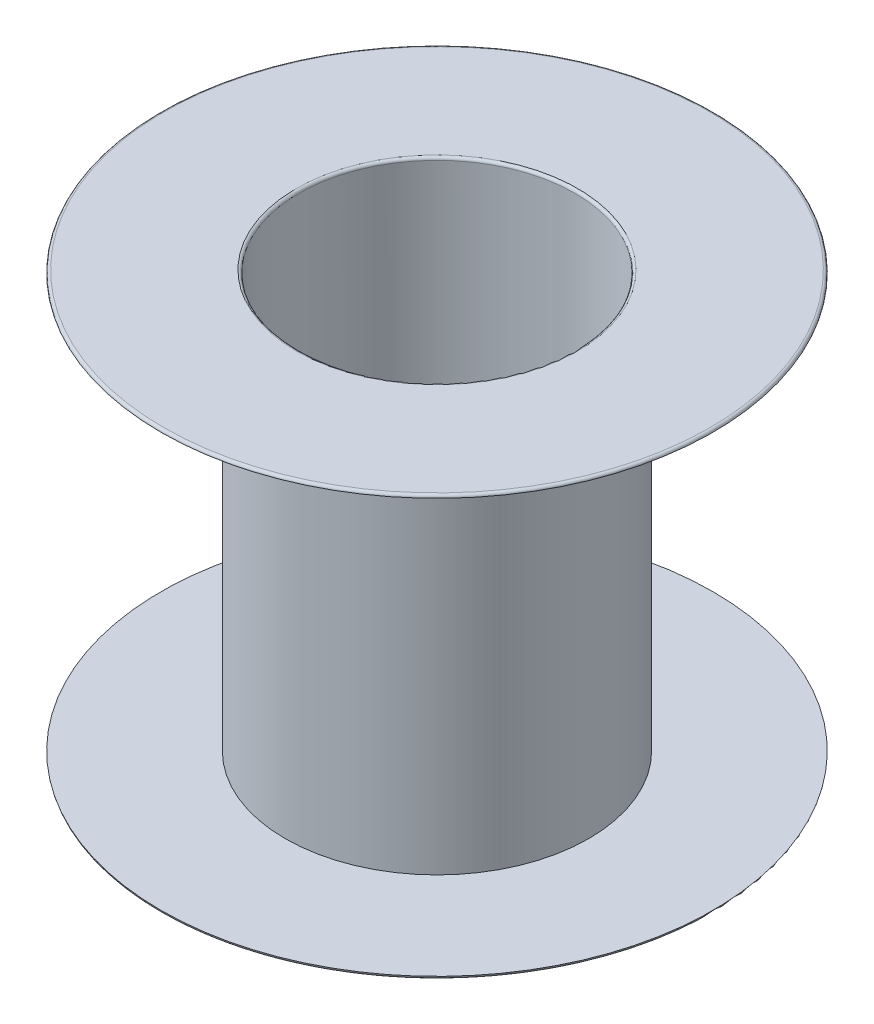
SolidWorks part; units mm, degrees
material "Copper"
ref_plane "Front" through (0, 0, 0) normal (0, 0, 1) x (1, 0, 0)
ref_plane "Top" through (0, 0, 0) normal (0, 1, 0) x (1, 0, 0)
ref_plane "Right" through (0, 0, 0) normal (1, 0, 0) x (0, 0, -1)
sketch "Sketch1" plane through (0, 0, 0) normal (0, 1, 0) x (1, 0, 0)
  circle A0 centre (0, 0) radius 0.5
  circle A1 centre (0, 0) radius 0.55
extrude "Boss-Extrude1" add sketch "Sketch1" along normal blind 1.5
ref_plane "Plane1" through (0, 0.75, 0) normal (0, 1, 0) x (1, 0, 0)
sketch "Sketch2" plane through (0, 1.5, 0) normal (0, 1, 0) x (1, 0, 0)
  circle A0 centre (0, 0) radius 0.5
  circle A1 centre (0, 0) radius 1
extrude "Boss-Extrude2" add sketch "Sketch2" along normal blind 0.01
fillet "Fillet1" radius 0.01 2 edges at (0, 1.51, 0.5) (0, 1.51, 1)
mirror "Mirror1" about plane through (0, 0.75, 0) normal (0, 1, 0) of "Boss-Extrude2", "Fillet1"
